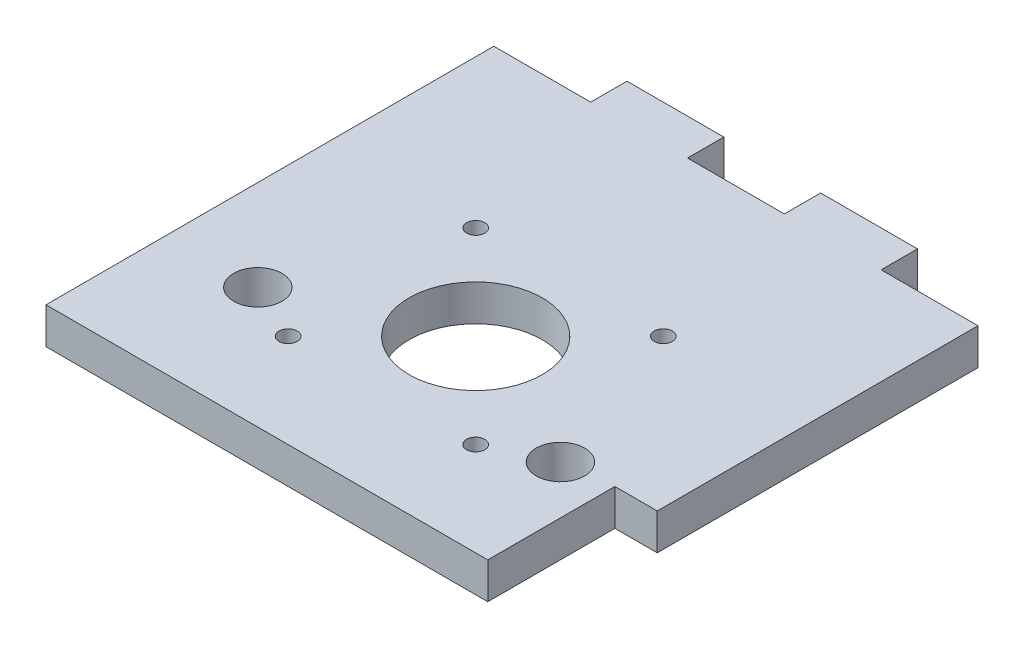
SolidWorks part; units mm, degrees
ref_plane "Front Plane" through (0, 0, 0) normal (0, 0, 1) x (1, 0, 0)
ref_plane "Top Plane" through (0, 0, 0) normal (0, 1, 0) x (1, 0, 0)
ref_plane "Right Plane" through (0, 0, 0) normal (1, 0, 0) x (0, 0, -1)
sketch "Sketch1" plane through (0, 0, 0) normal (0, 1, 0) x (1, 0, 0)
  line L0 (-1000, 0) -> (49000, 0) construction
  line L5 (0, -1000) -> (0, 49000) construction
  line L6 (-40, 43) -> (-24, 43)
  line L7 (-40, -31) -> (40, -31)
  line L8 (-40, -31) -> (-40, 43)
  line L9 (-24, 49) -> (-8, 49)
  line L10 (40, -31) -> (40, 43)
  line L11 (-24, 49) -> (-24, 43)
  line L12 (-8, 49) -> (-8, 43)
  line L13 (8, 49) -> (8, 43)
  line L14 (24, 49) -> (24, 43)
  line L16 (24, 43) -> (40, 43)
  line L17 (8, 49) -> (24, 49)
  line L18 (-8, 43) -> (8, 43)
  circle A10 centre (0, 0) radius 4
  circle A11 centre (15.5, 15.5) radius 1.5
  circle A12 centre (-15.5, 15.5) radius 1.5
  circle A13 centre (-15.5, -15.5) radius 1.5
  circle A14 centre (15.5, -15.5) radius 1.5
  circle A16 centre (-25, -11) radius 4
  circle A17 centre (25, -11) radius 4
  point P6 (0, 43)
  dimension "D3" = 8
  dimension "D4" = 15.5
  dimension "D6" = 3
  dimension "D12" = 25
  dimension "D13" = 31
  dimension "D2" = 80
  dimension "D5" = 15.5
  dimension "D7" = 6
  dimension "D9" = 4
  dimension "D8" = 16
  dimension "D10" = 16
  dimension "D11" = 80
  dimension "D14" = 20
extrude "Boss-Extrude1" add sketch "Sketch1" along normal blind 6
sketch "Sketch2" plane through (0, 6, 0) normal (0, 1, 0) x (1, 0, 0)
  circle A0 centre (0, 0) radius 11
  dimension "D1" = 22
extrude "Cut-Extrude1" cut sketch "Sketch2" against normal up to next
sketch "Sketch3" plane through (40, 0, 0) normal (1, 0, 0) x (0, 0, -1)
  line L0 (-31, 6) -> (43, 6) construction
  line L1 (-31, 0) -> (-10, 0)
  line L2 (-31, 0) -> (-31, 6)
  line L3 (-31, 6) -> (-10, 6)
  line L4 (-10, 0) -> (-10, 6)
  dimension "D1" = 21
extrude "Cut-Extrude2" cut sketch "Sketch3" against normal blind 7
